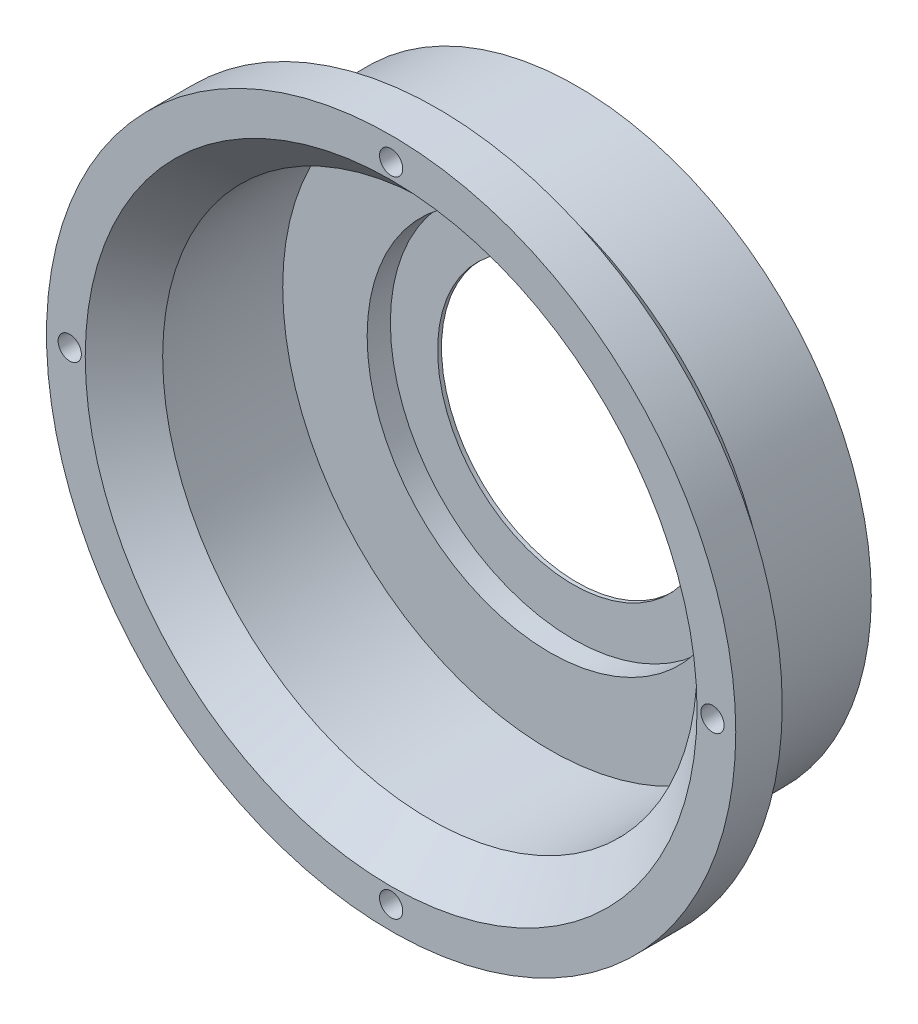
SolidWorks part; units mm, degrees
material "Custom Plastic"
ref_plane "Front Plane" through (0, 0, 0) normal (0, 0, 1) x (1, 0, 0)
ref_plane "Top Plane" through (0, 0, 0) normal (0, 1, 0) x (1, 0, 0)
ref_plane "Right Plane" through (0, 0, 0) normal (1, 0, 0) x (0, 0, -1)
sketch "Sketch1" plane through (0, 0, 0) normal (0, 0, 1) x (1, 0, 0)
  circle A0 centre (0, 0) radius 38
  dimension "D1" = 76
extrude "Boss-Extrude1" add sketch "Sketch1" along normal blind 24
shell "Shell1" thickness 3.5 removed face at (38, 0, 24)
sketch "Sketch2" plane through (0, 0, 3.5) normal (0, 0, 1) x (1, 0, 0)
  circle A0 centre (0, 0) radius 23.6
  dimension "D1" = 47.2
extrude "Cut-Extrude1" cut sketch "Sketch2" against normal blind 3
sketch "Sketch3" plane through (0, 0, 0.5) normal (0, 0, 1) x (1, 0, 0)
  circle A0 centre (0, 0) radius 17.5
  dimension "D1" = 35
extrude "Cut-Extrude2" cut sketch "Sketch3" against normal up to surface (0.5 mm away) up to face at (38, 0, 0)
sketch "Sketch4" plane through (0, 0, 24) normal (0, 0, 1) x (1, 0, 0)
  circle A0 centre (0, 0) radius 44.5
  circle A1 centre (0, 0) radius 38 construction
  circle A2 centre (0, 0) radius 38
  dimension "D1" = 89
extrude "Boss-Extrude2" add sketch "Sketch4" against normal blind 6
sketch "Sketch5" plane through (0, 0, 24) normal (0, 0, 1) x (1, 0, 0)
  circle A0 centre (0, 0) radius 41.5 construction
  circle A1 centre (0, -41.5) radius 1.5
  circle A2 centre (-41.5, 0) radius 1.5
  circle A3 centre (0, 41.5) radius 1.5
  circle A4 centre (41.5, 0) radius 1.5
  point P14 (0, 0)
  dimension "D1" = 83
  dimension "D2" = 3
  dimension "D3" = 4
extrude "Cut-Extrude3" cut sketch "Sketch5" against normal up to surface (6 mm away) up to face at (38, 0, 18)
chamfer "Chamfer1" distance 5 angle 45 1 edges at (34.5, 0, 24)
chamfer "Chamfer2" distance 5 angle 45 1 edges at (38, 0, 18)
